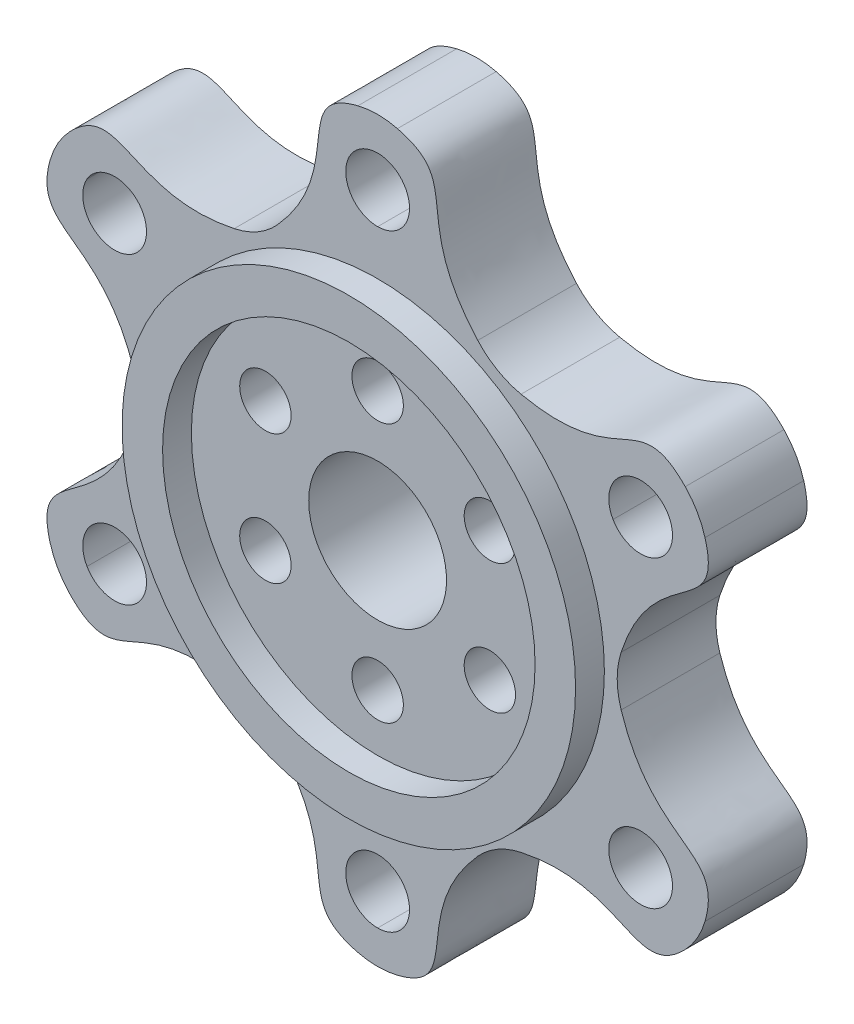
SolidWorks part; units mm, degrees
ref_plane "Front Plane" through (0, 0, 0) normal (0, 0, 1) x (1, 0, 0)
ref_plane "Top Plane" through (0, 0, 0) normal (0, 1, 0) x (1, 0, 0)
ref_plane "Right Plane" through (0, 0, 0) normal (1, 0, 0) x (0, 0, -1)
sketch "Sketch1" plane through (0, 0, 0) normal (0, 0, 1) x (1, 0, 0)
  line L0 (0, -55) -> (0, 55) construction
  line L1 (0, 0) -> (0, 45.72) construction
  circle A0 centre (0, 0) radius 8.509
  circle A1 centre (0, 0) radius 45.72
  circle A2 centre (0, 16.002) radius 3.175
  circle A3 centre (13.8581, 8.001) radius 3.175
  circle A4 centre (13.8581, -8.001) radius 3.175
  circle A5 centre (0, -16.002) radius 3.175
  circle A6 centre (-13.8581, -8.001) radius 3.175
  circle A7 centre (-13.8581, 8.001) radius 3.175
  circle A8 centre (0, 37.5) radius 3.937
  circle A10 centre (32.476, 18.75) radius 3.937
  circle A11 centre (32.476, -18.75) radius 3.937
  circle A12 centre (0, -37.5) radius 3.937
  circle A13 centre (-32.476, -18.75) radius 3.937
  circle A14 centre (-32.476, 18.75) radius 3.937
  point P21 (0, 0)
  point P36 (0, 0)
  dimension "D1" = 17.018
  dimension "D2" = 91.44
  dimension "D3" = 6.35
  dimension "D6" = 7.874
  dimension "D4" = 16.002
  dimension "D8" = 37.5
  dimension "D5" = 6
  dimension "D7" = 6
extrude "Boss-Extrude3" add sketch "Sketch1" along normal blind 12.192
sketch "Sketch2" plane through (0, 0, 12.192) normal (0, 0, 1) x (1, 0, 0)
  line L0 (0, -55) -> (0, 55) construction
  line L1 (-32.476, 18.75) -> (0, 37.5) construction
  line L2 (-16.238, 28.125) -> (-4.2545, 7.369) construction
  line L3 (16.1981, 28.148) -> (4.2146, 7.3919) construction
  line L6 (32.476, -18.75) -> (32.476, 18.75) construction
  line L7 (32.476, 18.75) -> (0, 37.5) construction
  line L8 (55, 0) -> (-55, 0) construction
  circle A0 centre (0, 0) radius 27.94 construction
  circle A1 centre (0, 0) radius 45.72 construction
  circle A2 centre (0, 0) radius 8.509 construction
  circle A3 centre (0, 0) radius 45.72
  spline S0 degree 3 poles (-14.625, 25.3312) (-1.5745, 37.1177) (-13.1193, 43.9586) (0, 45.72) knots 0 0 0 0 1 1 1 1
  spline S1 degree 3 poles (14.625, 25.3312) (1.5745, 37.1177) (13.1193, 43.9586) (0, 45.72) knots 0 0 0 0 1 1 1 1
  spline S2 degree 3 poles (-29.25, 0) (-32.9321, 17.1953) (-44.6289, 10.6177) (-39.5947, 22.86) knots 0 0 0 0 1 1 1 1
  spline S3 degree 3 poles (-14.625, 25.3312) (-31.3576, 19.9224) (-31.5096, 33.3409) (-39.5947, 22.86) knots 0 0 0 0 1 1 1 1
  spline S4 degree 3 poles (-14.625, -25.3312) (-31.3576, -19.9224) (-31.5096, -33.3409) (-39.5947, -22.86) knots 0 0 0 0 1 1 1 1
  spline S5 degree 3 poles (-29.25, 0) (-32.9321, -17.1953) (-44.6289, -10.6177) (-39.5947, -22.86) knots 0 0 0 0 1 1 1 1
  spline S6 degree 3 poles (14.625, -25.3312) (31.3576, -19.9224) (31.5096, -33.3409) (39.5947, -22.86) knots 0 0 0 0 1 1 1 1
  spline S7 degree 3 poles (29.25, 0) (32.9321, -17.1953) (44.6289, -10.6177) (39.5947, -22.86) knots 0 0 0 0 1 1 1 1
  spline S8 degree 3 poles (14.625, -25.3312) (1.5745, -37.1177) (13.1193, -43.9586) (0, -45.72) knots 0 0 0 0 1 1 1 1
  spline S9 degree 3 poles (-14.625, -25.3312) (-1.5745, -37.1177) (-13.1193, -43.9586) (0, -45.72) knots 0 0 0 0 1 1 1 1
  spline S10 degree 3 poles (29.25, 0) (32.9321, 17.1953) (44.6289, 10.6177) (39.5947, 22.86) knots 0 0 0 0 1 1 1 1
  spline S11 degree 3 poles (14.625, 25.3312) (31.3576, 19.9224) (31.5096, 33.3409) (39.5947, 22.86) knots 0 0 0 0 1 1 1 1
  point P5 (-16.238, 28.125)
  point P6 (16.1981, 28.148)
  circle M8 centre (0, 0) radius 45.72
  dimension "D1" = 55.88
  dimension "D2" = 18.796
  dimension "D3" = 29.25
extrude "Cut-Extrude1" cut sketch "Sketch2" against normal blind 22.86 contours S1 S11 M8 | S5 S2 A3 | S10 S7 A3 | S6 S8 A3 | S9 S4 M8 | S3 S0 M8 region at (38.672, 0, 12.192) region at (19.336, 33.4909, 12.192) region at (19.336, -33.4909, 12.192) region at (-19.336, 33.4909, 12.192) region at (-19.336, -33.4909, 12.192) region at (-38.672, 0, 12.192)
sketch "Sketch4" plane through (0, 0, 12.192) normal (0, 0, 1) x (1, 0, 0)
  circle A0 centre (0, 0) radius 8.509 construction
  circle A1 centre (0, 0) radius 8.509 construction
  circle A2 centre (0, 0) radius 28
  circle A3 centre (0, 0) radius 23
  dimension "D1" = 56
  dimension "D2" = 46
extrude "Boss-Extrude4" add sketch "Sketch4" along normal blind 3.556 contours A2 | A3
ref_plane "Plane1" through (0, 0, 0) normal (1, 0, 0) x (0, 0, -1)
ref_plane "Plane2" through (0, 0, 0) normal (-0.5, -0.866, 0) x (-0.866, 0.5, 0)
ref_plane "Plane3" through (0, 0, 0) normal (-0.5, 0.866, 0) x (0.866, 0.5, 0)
split line "Split Line1"
split line "Split Line2"
split line "Split Line3"
ref_axis "Axis1" through (0, 0, 12.192) along (0, 0, -1)
fillet "Fillet1" radius 10 12 edges at (29.25, 0, 6.096) (39.5947, -22.86, 6.096) (0, -45.72, 6.096) (14.625, -25.3312, 6.096) (-14.625, -25.3312, 6.096) (-39.5947, -22.86, 6.096) (-29.25, 0, 6.096) (-39.5947, 22.86, 6.096) (-14.625, 25.3312, 6.096) (14.625, 25.3312, 6.096) (39.5947, 22.86, 6.096) (0, 45.72, 6.096)
